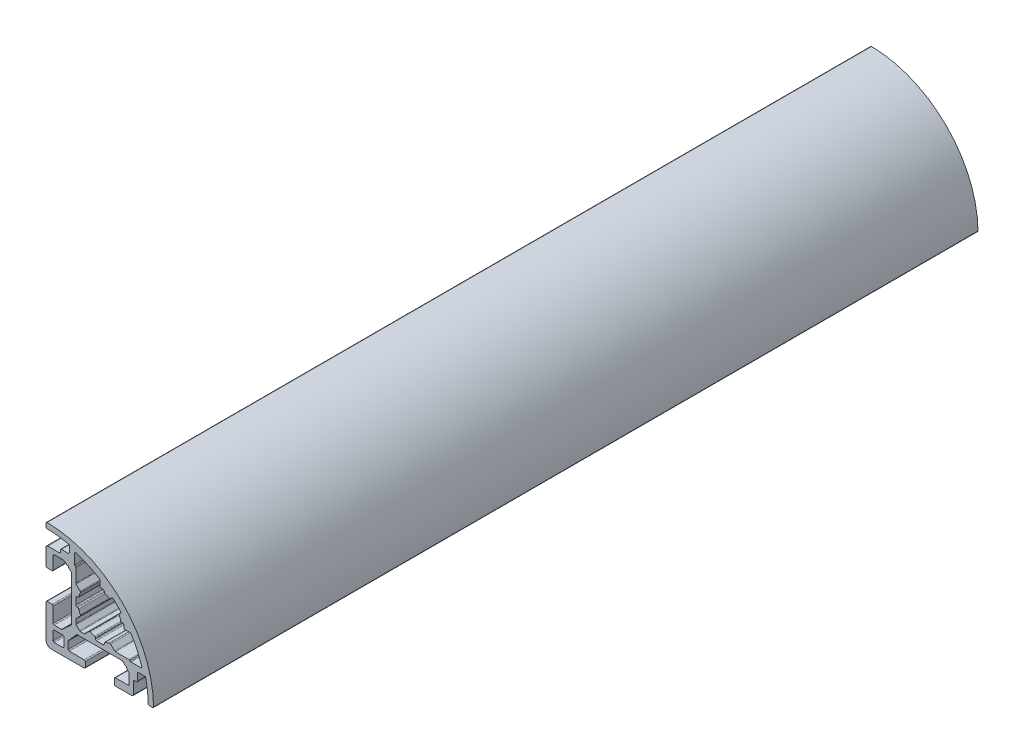
SolidWorks part; units mm, degrees
ref_plane "Plano frontal" through (0, 0, 0) normal (0, 0, 1) x (1, 0, 0)
ref_plane "Plano superior" through (0, 0, 0) normal (0, 1, 0) x (1, 0, 0)
ref_plane "Plano direito" through (0, 0, 0) normal (1, 0, 0) x (0, 0, -1)
ref_plane "Plano1" through (0, 0, 0) normal (0, 0, -1) x (-1, 0, 0)
sketch "Esboço1" plane through (0, 0, 0) normal (0, 0, -1) x (-1, 0, 0)
  line L0 (12.7, -13) -> (10.3, -13)
  line L1 (10, -12.7) -> (10, -10.3)
  line L2 (10.3, -10) -> (12.7, -10)
  line L3 (13, -10.3) -> (13, -12.7)
  line L4 (-0.95, 6.7) -> (-0.3, 6.7)
  line L5 (0, 7) -> (0, 8.4776)
  line L6 (7, 11.4273) -> (7, 8.6799)
  line L7 (6.9121, 8.4678) -> (6.7879, 8.3435)
  line L8 (6.7, 8.1314) -> (6.7, 4.3494)
  line L9 (6.6121, 4.1372) -> (5.4871, 3.0123)
  line L10 (6.1579, 1.25) -> (6.4, 1.25)
  line L11 (6.7, 0.95) -> (6.7, -0.95)
  line L12 (6.4, -1.25) -> (6.1579, -1.25)
  line L13 (5.4871, -3.0123) -> (6.6121, -4.1372)
  line L14 (6.7, -4.3494) -> (6.7, -5.4396)
  line L15 (6.6121, -5.6517) -> (5.6517, -6.6121)
  line L16 (5.4395, -6.7) -> (4.3494, -6.7)
  line L17 (4.1373, -6.6121) -> (3.0123, -5.4871)
  line L18 (1.25, -6.1579) -> (1.25, -6.4)
  line L19 (0.95, -6.7) -> (-0.95, -6.7)
  line L20 (-1.25, -6.4) -> (-1.25, -6.1579)
  line L21 (-3.0123, -5.4871) -> (-4.1373, -6.6121)
  line L22 (-4.3494, -6.7) -> (-8.1314, -6.7)
  line L23 (-8.3435, -6.7879) -> (-8.4678, -6.9121)
  line L24 (-8.6799, -7) -> (-11.4273, -7)
  line L25 (-8.4777, 0) -> (-7, 0)
  line L26 (-6.7, 0.3) -> (-6.7, 0.95)
  line L27 (-6.4, 1.25) -> (-6.1579, 1.25)
  line L28 (-5.4871, 3.0123) -> (-5.7974, 3.3226)
  line L29 (-3.3226, 5.7974) -> (-3.0123, 5.4871)
  line L30 (-1.25, 6.1579) -> (-1.25, 6.4)
  line L31 (7.9882, 6.432) -> (8.7045, 7.072)
  line L32 (8.7045, 7.072) -> (8.7283, 7.4958)
  line L33 (8.7283, 7.4958) -> (9.1516, 7.472)
  line L34 (9.1516, 7.472) -> (9.8678, 8.112)
  line L35 (10.08, 8.1999) -> (12.7001, 8.1998)
  line L36 (13.0001, 7.8998) -> (13, 4.3499)
  line L37 (13.3, 4.0499) -> (14.7, 4.0498)
  line L38 (15, 4.3498) -> (15, 8.8999)
  line L39 (14.5, 9.3999) -> (11.3, 9.3999)
  line L40 (11, 9.6999) -> (11, 10.1999)
  line L41 (10.7, 10.4999) -> (8.8, 10.4999)
  line L42 (8.5, 10.7999) -> (8.5, 12.51)
  line L43 (15, 13.7984) -> (15, 14.6985)
  line L44 (-14.6985, -15) -> (-13.7984, -15)
  line L45 (-12.5105, -8.5) -> (-10.8005, -8.5)
  line L46 (-10.5005, -8.8) -> (-10.5005, -10.7)
  line L47 (-10.2005, -11) -> (-9.7004, -11)
  line L48 (-9.4004, -11.3) -> (-9.4004, -14.5)
  line L49 (-8.9004, -15) -> (-4.3505, -15)
  line L50 (-4.0505, -14.7) -> (-4.0504, -13.3)
  line L51 (-4.3504, -13) -> (-7.9005, -12.9999)
  line L52 (-8.2005, -12.6999) -> (-8.2004, -10.0799)
  line L53 (-8.1126, -9.8677) -> (-7.4725, -9.1515)
  line L54 (-7.4725, -9.1515) -> (-7.4963, -8.728)
  line L55 (-7.4963, -8.728) -> (-7.0727, -8.7042)
  line L56 (-7.0727, -8.7042) -> (-6.4326, -7.988)
  line L57 (-6.2205, -7.9001) -> (6.2197, -7.9001)
  line L58 (6.4318, -7.988) -> (8.7117, -10.4679)
  line L59 (8.7996, -10.6801) -> (8.7996, -12.7001)
  line L60 (8.4996, -13.0001) -> (4.3496, -13.0001)
  line L61 (4.0496, -13.3001) -> (4.0496, -14.7)
  line L62 (4.3496, -15) -> (13.5, -15)
  line L63 (15, -13.5) -> (15, -4.3503)
  line L64 (14.7, -4.0503) -> (13.2999, -4.0503)
  line L65 (12.9999, -4.3503) -> (12.9999, -8.5003)
  line L66 (12.6999, -8.8003) -> (10.6798, -8.8003)
  line L67 (10.4677, -8.7124) -> (7.9878, -6.4325)
  line L68 (7.9003, -6.2203) -> (7.9003, 6.2198)
  arc A0 (10.3, -13) -> (10, -12.7) centre (10.3, -12.7) cw
  arc A1 (10, -10.3) -> (10.3, -10) centre (10.3, -10.3) cw
  arc A2 (12.7, -10) -> (13, -10.3) centre (12.7, -10.3) cw
  arc A3 (13, -12.7) -> (12.7, -13) centre (12.7, -12.7) cw
  arc A4 (-0.3, 6.7) -> (0, 7) centre (-0.3, 7) ccw
  arc A5 (0, 8.4776) -> (0.1408, 8.7319) centre (0.3, 8.4776) cw
  arc A6 (0.1408, 8.7319) -> (6.6101, 11.7135) centre (15, -15) cw
  arc A7 (6.6101, 11.7135) -> (7, 11.4273) centre (6.7, 11.4273) cw
  arc A8 (7, 8.6799) -> (6.9121, 8.4678) centre (6.7, 8.6799) cw
  arc A9 (6.7879, 8.3435) -> (6.7, 8.1314) centre (7, 8.1314) ccw
  arc A10 (6.7, 4.3494) -> (6.6121, 4.1372) centre (6.4, 4.3494) cw
  arc A11 (5.4871, 3.0123) -> (5.43, 2.6678) centre (5.6993, 2.8001) ccw
  arc A12 (5.43, 2.6678) -> (5.867, 1.4768) centre (0, 0) cw
  arc A13 (5.867, 1.4768) -> (6.1579, 1.25) centre (6.1579, 1.55) ccw
  arc A14 (6.4, 1.25) -> (6.7, 0.95) centre (6.4, 0.95) cw
  arc A15 (6.7, -0.95) -> (6.4, -1.25) centre (6.4, -0.95) cw
  arc A16 (6.1579, -1.25) -> (5.867, -1.4768) centre (6.1579, -1.55) ccw
  arc A17 (5.867, -1.4768) -> (5.43, -2.6678) centre (0, 0) cw
  arc A18 (5.43, -2.6678) -> (5.4871, -3.0123) centre (5.6993, -2.8001) ccw
  arc A19 (6.6121, -4.1372) -> (6.7, -4.3494) centre (6.4, -4.3494) cw
  arc A20 (6.7, -5.4396) -> (6.6121, -5.6517) centre (6.4, -5.4396) cw
  arc A21 (5.6517, -6.6121) -> (5.4395, -6.7) centre (5.4395, -6.4) cw
  arc A22 (4.3494, -6.7) -> (4.1373, -6.6121) centre (4.3494, -6.4) cw
  arc A23 (3.0123, -5.4871) -> (2.6678, -5.43) centre (2.8001, -5.6993) ccw
  arc A24 (2.6678, -5.43) -> (1.4768, -5.867) centre (0, 0) cw
  arc A25 (1.4768, -5.867) -> (1.25, -6.1579) centre (1.55, -6.1579) ccw
  arc A26 (1.25, -6.4) -> (0.95, -6.7) centre (0.95, -6.4) cw
  arc A27 (-0.95, -6.7) -> (-1.25, -6.4) centre (-0.95, -6.4) cw
  arc A28 (-1.25, -6.1579) -> (-1.4768, -5.867) centre (-1.55, -6.1579) ccw
  arc A29 (-1.4768, -5.867) -> (-2.6678, -5.43) centre (0, 0) cw
  arc A30 (-2.6678, -5.43) -> (-3.0123, -5.4871) centre (-2.8001, -5.6993) ccw
  arc A31 (-4.1373, -6.6121) -> (-4.3494, -6.7) centre (-4.3494, -6.4) cw
  arc A32 (-8.1314, -6.7) -> (-8.3435, -6.7879) centre (-8.1314, -7) ccw
  arc A33 (-8.4678, -6.9121) -> (-8.6799, -7) centre (-8.6799, -6.7) cw
  arc A34 (-11.4273, -7) -> (-11.7135, -6.6101) centre (-11.4273, -6.7) cw
  arc A35 (-11.7135, -6.6101) -> (-8.7319, -0.1408) centre (15, -15) cw
  arc A36 (-8.7319, -0.1408) -> (-8.4777, 0) centre (-8.4777, -0.3) cw
  arc A37 (-7, 0) -> (-6.7, 0.3) centre (-7, 0.3) ccw
  arc A38 (-6.7, 0.95) -> (-6.4, 1.25) centre (-6.4, 0.95) cw
  arc A39 (-6.1579, 1.25) -> (-5.867, 1.4768) centre (-6.1579, 1.55) ccw
  arc A40 (-5.867, 1.4768) -> (-5.43, 2.6678) centre (0, 0) cw
  arc A41 (-5.43, 2.6678) -> (-5.4871, 3.0123) centre (-5.6993, 2.8001) ccw
  arc A42 (-5.7974, 3.3226) -> (-5.8083, 3.7354) centre (-5.5853, 3.5347) cw
  arc A43 (-5.8083, 3.7354) -> (-3.7354, 5.8083) centre (15, -15) cw
  arc A44 (-3.7354, 5.8083) -> (-3.3226, 5.7974) centre (-3.5347, 5.5853) cw
  arc A45 (-3.0123, 5.4871) -> (-2.6678, 5.43) centre (-2.8001, 5.6993) ccw
  arc A46 (-2.6678, 5.43) -> (-1.4768, 5.867) centre (0, 0) cw
  arc A47 (-1.4768, 5.867) -> (-1.25, 6.1579) centre (-1.55, 6.1579) ccw
  arc A48 (-1.25, 6.4) -> (-0.95, 6.7) centre (-0.95, 6.4) cw
  arc A49 (9.8678, 8.112) -> (10.08, 8.1999) centre (10.08, 7.8999) cw
  arc A50 (12.7001, 8.1998) -> (13.0001, 7.8998) centre (12.7001, 7.8998) cw
  arc A51 (13, 4.3499) -> (13.3, 4.0499) centre (13.3, 4.3499) ccw
  arc A52 (14.7, 4.0498) -> (15, 4.3498) centre (14.7, 4.3498) ccw
  arc A53 (15, 8.8999) -> (14.5, 9.3999) centre (14.5, 8.8999) ccw
  arc A54 (11.3, 9.3999) -> (11, 9.6999) centre (11.3, 9.6999) cw
  arc A55 (11, 10.1999) -> (10.7, 10.4999) centre (10.7, 10.1999) ccw
  arc A56 (8.8, 10.4999) -> (8.5, 10.7999) centre (8.8, 10.7999) cw
  arc A57 (8.5, 12.51) -> (8.734, 12.8026) centre (8.8, 12.51) cw
  arc A58 (8.734, 12.8026) -> (14.7031, 13.4984) centre (15, -15) cw
  arc A59 (14.7031, 13.4984) -> (15, 13.7984) centre (14.7, 13.7984) ccw
  arc A60 (15, 14.6985) -> (14.697, 14.9985) centre (14.7, 14.6985) ccw
  arc A61 (14.697, 14.9985) -> (-14.9985, -14.697) centre (15, -15) ccw
  arc A62 (-14.9985, -14.697) -> (-14.6985, -15) centre (-14.6985, -14.7) ccw
  arc A63 (-13.7984, -15) -> (-13.4985, -14.7031) centre (-13.7984, -14.7) ccw
  arc A64 (-13.4985, -14.7031) -> (-12.8027, -8.734) centre (15, -15) cw
  arc A65 (-12.8027, -8.734) -> (-12.5105, -8.5) centre (-12.51, -8.8) cw
  arc A66 (-10.8005, -8.5) -> (-10.5005, -8.8) centre (-10.8005, -8.8) cw
  arc A67 (-10.5005, -10.7) -> (-10.2005, -11) centre (-10.2005, -10.7) ccw
  arc A68 (-9.7004, -11) -> (-9.4004, -11.3) centre (-9.7004, -11.3) cw
  arc A69 (-9.4004, -14.5) -> (-8.9004, -15) centre (-8.9004, -14.5) ccw
  arc A70 (-4.3505, -15) -> (-4.0505, -14.7) centre (-4.3505, -14.7) ccw
  arc A71 (-4.0504, -13.3) -> (-4.3504, -13) centre (-4.3504, -13.3) ccw
  arc A72 (-7.9005, -12.9999) -> (-8.2005, -12.6999) centre (-7.9005, -12.6999) cw
  arc A73 (-8.2004, -10.0799) -> (-8.1126, -9.8677) centre (-7.9004, -10.0799) cw
  arc A74 (-6.4326, -7.988) -> (-6.2205, -7.9001) centre (-6.2205, -8.2001) cw
  arc A75 (6.2197, -7.9001) -> (6.4318, -7.988) centre (6.2197, -8.2001) cw
  arc A76 (8.7117, -10.4679) -> (8.7996, -10.6801) centre (8.4996, -10.6801) cw
  arc A77 (8.7996, -12.7001) -> (8.4996, -13.0001) centre (8.4996, -12.7001) cw
  arc A78 (4.3496, -13.0001) -> (4.0496, -13.3001) centre (4.3496, -13.3001) ccw
  arc A79 (4.0496, -14.7) -> (4.3496, -15) centre (4.3496, -14.7) ccw
  arc A80 (13.5, -15) -> (15, -13.5) centre (13.5, -13.5) ccw
  arc A81 (15, -4.3503) -> (14.7, -4.0503) centre (14.7, -4.3503) ccw
  arc A82 (13.2999, -4.0503) -> (12.9999, -4.3503) centre (13.2999, -4.3503) ccw
  arc A83 (12.9999, -8.5003) -> (12.6999, -8.8003) centre (12.6999, -8.5003) cw
  arc A84 (10.6798, -8.8003) -> (10.4677, -8.7124) centre (10.6798, -8.5003) cw
  arc A85 (7.9878, -6.4325) -> (7.9003, -6.2203) centre (8.2003, -6.2208) cw
  arc A86 (7.9003, 6.2198) -> (7.9882, 6.432) centre (8.2003, 6.2198) cw
  dimension "D1" = 30
  dimension "D2" = 1.5
extrude "Ressalto-extrusão1" add sketch "Esboço1" against normal blind 230
